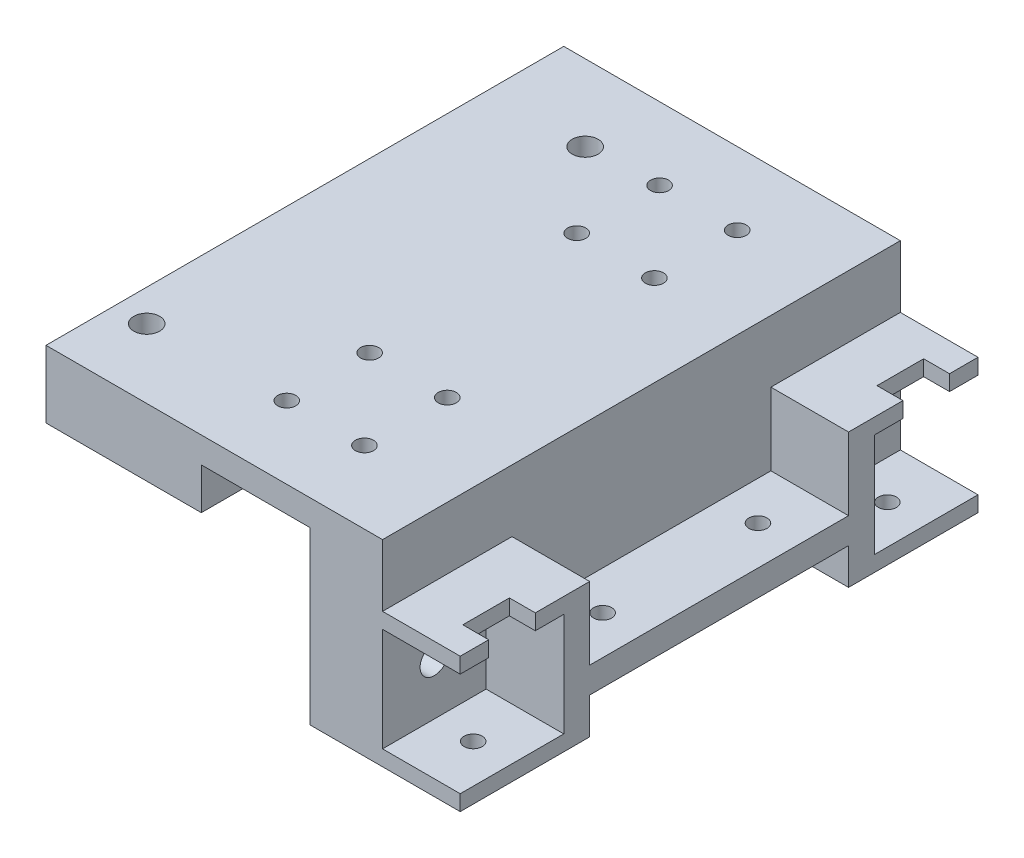
SolidWorks part; units mm, degrees
ref_plane "Front Plane" through (0, 0, 0) normal (0, 0, 1) x (1, 0, 0)
ref_plane "Top Plane" through (0, 0, 0) normal (0, 1, 0) x (1, 0, 0)
ref_plane "Right Plane" through (0, 0, 0) normal (1, 0, 0) x (0, 0, -1)
sketch "Sketch1" plane through (0, 0, 0) normal (0, 1, 0) x (1, 0, 0)
  line L0 (0, 50) -> (0, -50) construction
  line L1 (-10, 50) -> (10, 50)
  line L2 (-10, 50) -> (-10, -50)
  line L3 (-10, -50) -> (10, -50)
  line L4 (10, 50) -> (10, -50) construction
  line L5 (-10, 50) -> (10, -50) construction
  line L6 (-10, -50) -> (10, 50) construction
  line L7 (-7.5, 36) -> (7.5, 36) construction
  line L8 (-7.5, 36) -> (7.5, 20) construction
  line L9 (-10, 0) -> (10, 0) construction
  line L10 (-7.5, -36) -> (7.5, -20) construction
  line L11 (-7.5, -36) -> (7.5, -36) construction
  line L12 (-7.5, 20) -> (7.5, 20) construction
  line L13 (10, 50) -> (11, 50)
  line L14 (11, 50) -> (11, -50)
  line L15 (11, -50) -> (10, -50)
  circle A0 centre (-7.5, 36) radius 1.75
  circle A1 centre (7.5, 36) radius 1.75
  circle A2 centre (-7.5, 20) radius 1.75
  circle A3 centre (7.5, 20) radius 1.75
  circle A4 centre (7.5, -20) radius 1.75
  circle A5 centre (-7.5, -20) radius 1.75
  circle A6 centre (7.5, -36) radius 1.75
  circle A7 centre (-7.5, -36) radius 1.75
  point P0 (0, 0)
  point P16 (0, 36)
  dimension "D2" = 3.5
  dimension "D1" = 20
  dimension "D3" = 15
  dimension "D4" = 16
  dimension "D5" = 100
  dimension "D6" = 20
  dimension "D7" = 1
extrude "Boss-Extrude1" add sketch "Sketch1" along normal blind 5
sketch "Sketch2" plane through (11, 0, 0) normal (1, 0, 0) x (0, 0, -1)
  line L1 (-50, 5) -> (50, 5)
  line L2 (-50, 5) -> (-50, -33)
  line L3 (-50, -33) -> (50, -33)
  line L5 (50, 5) -> (50, -33)
  line L6 (50, 5) -> (50, 0) construction
  line L7 (-50, 5) -> (-50, 0) construction
  line L8 (-50, 5) -> (50, 5) construction
  dimension "D1" = 38
extrude "Boss-Extrude2" add sketch "Sketch2" along normal blind 14
sketch "Sketch3" plane through (25, 0, 0) normal (1, 0, 0) x (0, 0, -1)
  line L0 (0, 5) -> (0, -33) construction
  line L1 (-25, -21) -> (25, -21)
  line L2 (-25, -21) -> (-25, -26)
  line L3 (-25, -26) -> (25, -26)
  line L4 (25, -21) -> (25, -26)
  line L5 (50, 5) -> (-50, 5) construction
  line L6 (-50, -33) -> (50, -33) construction
  point P10 (0, -21)
  dimension "D1" = 5
  dimension "D2" = 50
  dimension "D3" = 7
extrude "Boss-Extrude3" add sketch "Sketch3" along normal blind 15
sketch "Sketch4" plane through (0, -21, 0) normal (0, 1, 0) x (1, 0, 0)
  line L0 (25, 0) -> (40, 0) construction
  line L1 (25, 25) -> (25, -25) construction
  line L2 (40, 25) -> (40, -25) construction
  line L3 (32.5, -15) -> (32.5, 15) construction
  circle A0 centre (32.5, 15) radius 1.75
  circle A1 centre (32.5, -15) radius 1.75
  point P8 (32.5, 0)
  dimension "D1" = 30
  dimension "D2" = 3.5
extrude "Cut-Extrude1" cut sketch "Sketch4" against normal through all
sketch "Sketch8" plane through (25, 0, 0) normal (1, 0, 0) x (0, 0, -1)
  line L0 (-50, 5) -> (-50, -33) construction
  line L1 (-50, -7) -> (-25, -7)
  line L2 (-50, -7) -> (-50, -10)
  line L3 (-50, -33) -> (-25, -33)
  line L4 (-25, -7) -> (-25, -33)
  line L5 (-50, -30) -> (-50, -33)
  line L6 (-50, -30) -> (-30, -30)
  line L8 (-50, -10) -> (-30, -10)
  line L9 (-30, -30) -> (-30, -10)
  line L10 (0, 20.9) -> (0, -20.9) construction
  line L11 (30, -30) -> (30, -10)
  line L12 (50, -10) -> (30, -10)
  line L13 (50, -30) -> (30, -30)
  line L14 (50, -30) -> (50, -33)
  line L15 (25, -7) -> (25, -33)
  line L16 (50, -33) -> (25, -33)
  line L17 (50, -7) -> (50, -10)
  line L18 (50, -7) -> (25, -7)
  line L19 (-50, -33) -> (50, -33) construction
  dimension "D1" = 3
  dimension "D2" = 5
  dimension "D3" = 3
  dimension "D4" = 20
  dimension "D5" = 20
extrude "Boss-Extrude6" add sketch "Sketch8" along normal blind 15
sketch "Sketch9" plane through (25, 0, 0) normal (1, 0, 0) x (0, 0, -1)
  line L0 (-50, -10) -> (-30, -30) construction
  line L1 (50, -10) -> (30, -30) construction
  circle A0 centre (-40, -20) radius 2.75
  circle A1 centre (40, -20) radius 2.75
  dimension "D1" = 5.5
extrude "Cut-Extrude3" cut sketch "Sketch9" against normal through all
sketch "Sketch10" plane through (11, 0, 0) normal (-1, 0, 0) x (0, 0, 1)
  circle A0 centre (-40, -20) radius 4.5
  circle A1 centre (40, -20) radius 4.5
  dimension "D1" = 9
extrude "Cut-Extrude4" cut sketch "Sketch10" against normal offset from surface (9 mm away) 5 up to face at (25, -20, 37.25)
sketch "Sketch11" plane through (0, -7, 0) normal (0, 1, 0) x (1, 0, 0)
  line L0 (40, -25) -> (40, -50) construction
  line L1 (40, -35.5) -> (35, -35.5)
  line L2 (40, -35.5) -> (40, -44.5)
  line L3 (40, -44.5) -> (35, -44.5)
  line L4 (35, -35.5) -> (35, -44.5)
  line L5 (35, -40) -> (40, -40) construction
  line L6 (40, -50) -> (25, -50) construction
  line L7 (-10, 0) -> (40, 0) construction
  line L8 (-10, 50) -> (-10, -50) construction
  line L9 (40, 25) -> (40, -25) construction
  line L10 (40, -35.5) -> (35, -35.5)
  line L11 (40, -44.5) -> (35, -44.5)
  line L12 (35, 40) -> (40, 40) construction
  line L13 (40, 44.5) -> (35, 44.5)
  line L14 (40, 35.5) -> (35, 35.5)
  line L15 (35, 35.5) -> (35, 44.5)
  line L16 (40, 44.5) -> (35, 44.5)
  line L17 (40, 35.5) -> (40, 44.5)
  line L18 (40, 35.5) -> (35, 35.5)
  line M7 (40, -50) -> (40, -25)
  dimension "D1" = 9
  dimension "D2" = 10
  dimension "D3" = 5
extrude "Cut-Extrude5" cut sketch "Sketch11" against normal up to next contours L1 L4 L3 M7 | L14 L17 L13 L15 region at (37.5, -7, 40) region at (37.5, -7, -40)
sketch "Sketch12" plane through (0, -30, 0) normal (0, 1, 0) x (1, 0, 0)
  line L0 (40, -40) -> (25, -40) construction
  line L1 (40, -30) -> (40, -50) construction
  line L2 (25, -25) -> (25, -50) construction
  line L3 (-20.9, 0) -> (20.9, 0) construction
  circle A0 centre (32.5, -40) radius 1.75
  circle A2 centre (32.5, 40) radius 1.75
  point P8 (32.5, -40)
  dimension "D1" = 3.5
extrude "Cut-Extrude6" cut sketch "Sketch12" against normal through all
sketch "Sketch13" plane through (-10, 0, 0) normal (-1, 0, 0) x (0, 0, 1)
  line L1 (-50, 5) -> (50, 5)
  line L2 (-50, 5) -> (-50, -8)
  line L3 (-50, -8) -> (50, -8)
  line L4 (50, 5) -> (50, -8)
  point P4 (50, 5)
  dimension "D1" = 13
extrude "Boss-Extrude7" add sketch "Sketch13" along normal blind 30
sketch "Sketch14" plane through (0, 5, 0) normal (0, 1, 0) x (1, 0, 0)
  line L0 (-40, -50) -> (25, -50) construction
  line L1 (-10.5, -50) -> (10.5, -50) construction
  line L2 (-10.5, -50) -> (-10.5, 50) construction
  line L3 (-10.5, 50) -> (10.5, 50) construction
  line L4 (10.5, -50) -> (10.5, 50) construction
  line L5 (25, 50) -> (-40, 50) construction
  line L6 (-27.5162, 35.2791) -> (-27.5162, -36.668) construction
  circle A0 centre (-21.15, 35.2791) radius 2.5
  circle A1 centre (-33.8824, -36.668) radius 2.5
  circle A2 centre (-33.8824, -36.668) radius 6.3662 construction
  circle A3 centre (-21.15, 35.2791) radius 6.3662 construction
  point P14 (0, 50)
  point P18 (-27.5162, -10.3868)
  point P19 (-27.5162, 11.354)
  point P20 (-33.8824, -0.5273)
  point P21 (0, 0)
  point P22 (0, 0)
  point P23 (-21.15, 35.2791)
  point P24 (-33.8824, -36.668)
  dimension "D1" = 5
  dimension "D2" = 5
  dimension "D4" = 21
  dimension "D5" = 12.7324
  dimension "D3" = 21.15
extrude "Cut-Extrude7" cut sketch "Sketch14" against normal through all
